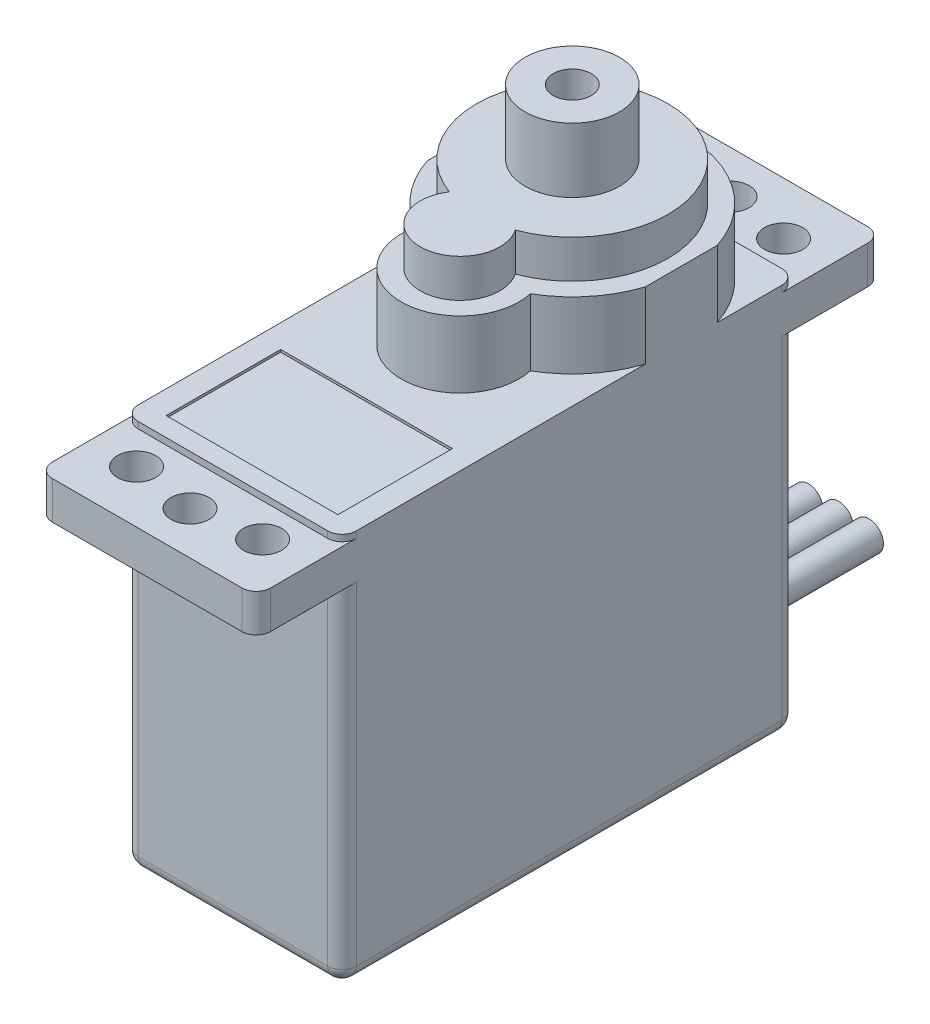
SolidWorks part; units mm, degrees
material "Mini Servo"
ref_plane "Front Plane" through (0, 0, 0) normal (0, 0, 1) x (1, 0, 0)
ref_plane "Top Plane" through (0, 0, 0) normal (0, 1, 0) x (1, 0, 0)
ref_plane "Right Plane" through (0, 0, 0) normal (1, 0, 0) x (0, 0, -1)
sketch "Sketch1" plane through (0, 0, 0) normal (1, 0, 0) x (0, 0, -1)
  line L0 (0, 10.25) -> (0, -10.25) construction
  line L1 (-11.8999, 10.25) -> (11.8999, 10.25)
  line L2 (-11.8999, 10.25) -> (-11.8999, -10.25)
  line L3 (-11.8999, -10.25) -> (11.8999, -10.25)
  line L4 (11.8999, 10.25) -> (11.8999, -10.25)
  dimension "D1" = 23.7998
  dimension "D2" = 20.5
extrude "Extrude1" add sketch "Sketch1" along normal blind 5.715 and the other way blind 5.715
sketch "Sketch2" plane through (0, 10.25, 0) normal (0, 1, 0) x (-1, 0, 0)
  line L3 (0, 0) -> (0, -5.8801) construction
  line L4 (0, 3.0861) -> (5.715, 3.0861) construction
  line L5 (-5.715, -11.8999) -> (5.715, -11.8999) construction
  line L6 (5.715, -11.8999) -> (5.715, 11.8999) construction
  line L7 (5.715, -7.7713) -> (5.715, -3.9889)
  line L8 (-5.715, -11.8999) -> (-5.715, 11.8999) construction
  line L9 (-5.715, -7.7713) -> (-5.715, -3.9889)
  arc A0 (-3.0128, -0.6685) -> (-5.715, -3.9889) centre (0, -5.8801) ccw
  arc A1 (3.0128, -0.6685) -> (-3.0128, -0.6685) centre (0, 0) ccw
  arc A2 (5.715, -3.9889) -> (3.0128, -0.6685) centre (0, -5.8801) ccw
  arc A3 (-5.715, -7.7713) -> (5.715, -7.7713) centre (0, -5.8801) ccw
  dimension "D2" = 6.1722
  dimension "D1" = 6.0198
extrude "Boss-Extrude7" add sketch "Sketch2" along normal blind 3.5
sketch "Sketch10" plane through (0, 13.75, 0) normal (0, 1, 0) x (1, 0, 0)
  line L4 (4.715, 4.1576) -> (4.715, 7.6026)
  line L5 (-4.715, 7.6026) -> (-4.715, 4.1576)
  arc A8 (-1.7289, 1.1674) -> (1.7289, 1.1674) centre (0, 0) ccw
  arc A9 (1.7289, 1.1674) -> (4.715, 4.1576) centre (0, 5.8801) ccw
  arc A10 (4.715, 7.6026) -> (-4.715, 7.6026) centre (0, 5.8801) ccw
  arc A11 (-4.715, 4.1576) -> (-1.7289, 1.1674) centre (0, 5.8801) ccw
  arc A12 (-1.7289, 1.1674) -> (1.7289, 1.1674) centre (0, 0) ccw
  arc A13 (1.7289, 1.1674) -> (-1.7289, 1.1674) centre (0, 5.8801) ccw
  dimension "D1" = 1
extrude "Boss-Extrude8" add sketch "Sketch10" along normal blind 2
sketch "Sketch3" plane through (5.715, 0, 0) normal (1, 0, 0) x (0, 0, -1)
  line L1 (-11.8999, 9.908) -> (-16.3957, 9.908)
  line L2 (-11.8999, 9.908) -> (-11.8999, 7.9268)
  line L3 (-11.8999, 7.9268) -> (-16.3957, 7.9268)
  line L4 (-16.3957, 9.908) -> (-16.3957, 7.9268)
  line L5 (-11.8999, 10.25) -> (-11.8999, -10.25) construction
  line L6 (0, 8.509) -> (0, -10.25) construction
  line L7 (11.8999, 9.908) -> (16.3957, 9.908)
  line L8 (11.8999, 9.908) -> (11.8999, 7.9268)
  line L9 (11.8999, 7.9268) -> (16.3957, 7.9268)
  line L10 (16.3957, 9.908) -> (16.3957, 7.9268)
  line L11 (-11.8999, -10.25) -> (11.8999, -10.25) construction
  line L12 (10.8999, 15.75) -> (1.1674, 15.75) construction
  dimension "D1" = 4.4958
  dimension "D2" = 1.9812
  dimension "D3" = 5.842
extrude "Extrude2" add sketch "Sketch3" against normal up to surface (11.43 mm away) up to face at (-5.715, 6.4375, -4.1911)
sketch "Sketch4" plane through (0, 9.908, 0) normal (0, 1, 0) x (1, 0, 0)
  line L0 (0, 16.3957) -> (0, -16.3957) construction
  line L1 (-5.715, 16.3957) -> (5.715, 16.3957) construction
  line L2 (-5.715, -16.3957) -> (5.715, -16.3957) construction
  line L3 (-5.715, 0) -> (5.715, 0) construction
  line L4 (-5.715, -11.8999) -> (-5.715, -16.3957) construction
  line L5 (5.715, -11.8999) -> (5.715, -16.3957) construction
  line L7 (-3.302, -13.65) -> (3.302, -13.65) construction
  line L8 (-3.302, -13.65) -> (-3.302, 13.65) construction
  line L9 (-3.302, 13.65) -> (3.302, 13.65) construction
  line L10 (3.302, -13.65) -> (3.302, 13.65) construction
  line L11 (-3.302, -13.65) -> (3.302, 13.65) construction
  line L12 (-3.302, 13.65) -> (3.302, -13.65) construction
  circle A0 centre (0, 14.15) radius 1
  circle A1 centre (0, -14.15) radius 1
  circle A2 centre (-3.302, 13.65) radius 1
  circle A3 centre (3.302, 13.65) radius 1
  circle A4 centre (3.302, -13.65) radius 1
  circle A5 centre (-3.302, -13.65) radius 1
  point P17 (0, 0)
  dimension "D2" = 2
  dimension "D1" = 28.3
  dimension "D3" = 6.604
  dimension "D4" = 27.3
extrude "Extrude3" cut sketch "Sketch4" against normal through all
sketch "Sketch5" plane through (0, 0, -11.8999) normal (0, 0, -1) x (-1, 0, 0)
  line L0 (0, 0) -> (0, -9.742) construction
  line L1 (-3.175, -9.742) -> (3.175, -9.742)
  line L2 (-3.175, -9.742) -> (-3.175, -5.297)
  line L3 (-3.175, -5.297) -> (3.175, -5.297)
  line L4 (3.175, -9.742) -> (3.175, -5.297)
  line L5 (-5.715, -10.25) -> (5.715, -10.25) construction
  dimension "D1" = 0.508
  dimension "D2" = 6.35
  dimension "D3" = 4.445
extrude "Boss-Extrude1" add sketch "Sketch5" along normal blind 1.5875
sketch "Sketch6" plane through (0, 0, -13.4874) normal (0, 0, -1) x (-1, 0, 0)
  line L0 (-3.175, -7.5195) -> (0, -7.5195) construction
  line L1 (-3.175, -5.297) -> (-3.175, -9.742) construction
  line L2 (0, -7.5195) -> (3.175, -7.5195) construction
  line L3 (3.175, -9.742) -> (3.175, -5.297) construction
  circle A0 centre (0, -7.5195) radius 0.762
  circle A1 centre (-1.5875, -7.5195) radius 0.762
  circle A2 centre (1.5875, -7.5195) radius 0.762
  dimension "D1" = 1.524
extrude "Boss-Extrude4" add sketch "Sketch6" along normal blind 6.35
sketch "Sketch8" plane through (0, 15.75, 0) normal (0, 1, 0) x (1, 0, 0)
  circle A0 centre (0, 5.8801) radius 2.4765
  arc A1 (1.7289, 1.1674) -> (-1.7289, 1.1674) centre (0, 5.8801) ccw construction
  dimension "D1" = 4.953
extrude "Boss-Extrude6" add sketch "Sketch8" along normal blind 3.3782
sketch "Sketch9" plane through (0, 10.25, 0) normal (0, 1, 0) x (1, 0, 0)
  line L0 (0, 0) -> (0, -11.8999) construction
  line L2 (-5.715, -11.8999) -> (5.715, -11.8999) construction
  line L3 (-4.5, -10.8999) -> (4.5, -10.8999)
  line L4 (-4.5, -10.8999) -> (-4.5, -4.8999)
  line L5 (-4.5, -4.8999) -> (4.5, -4.8999)
  line L6 (4.5, -10.8999) -> (4.5, -4.8999)
  line L7 (-4.5, -10.8999) -> (4.5, -4.8999) construction
  line L8 (-4.5, -4.8999) -> (4.5, -10.8999) construction
  line L9 (5.715, -11.8999) -> (-5.715, -11.8999) construction
  point P5 (0, -7.8999)
  dimension "D1" = 6
  dimension "D2" = 9
  dimension "D3" = 1
extrude "Cut-Extrude2" cut sketch "Sketch9" against normal blind 0.125
sketch "Sketch11" plane through (0, 19.1282, 0) normal (0, 1, 0) x (1, 0, 0)
  circle A0 centre (0, 5.8801) radius 1
  dimension "D1" = 2
extrude "Cut-Extrude3" cut sketch "Sketch11" against normal blind 2
fillet "Fillet1" radius 0.75 16 edges at (-5.715, 8.9174, -16.3957) (-5.715, -1.1616, -11.8999) (-5.715, 10.079, -11.8999) (5.715, 8.9174, -16.3957) (5.715, 10.079, -11.8999) (5.715, 8.9174, 16.3957) (-5.715, 8.9174, 16.3957) (0, -10.25, 11.8999) (0, -10.25, -11.8999) (-5.715, -10.25, 0) (5.715, -10.25, 0) (5.715, -1.1616, -11.8999)
